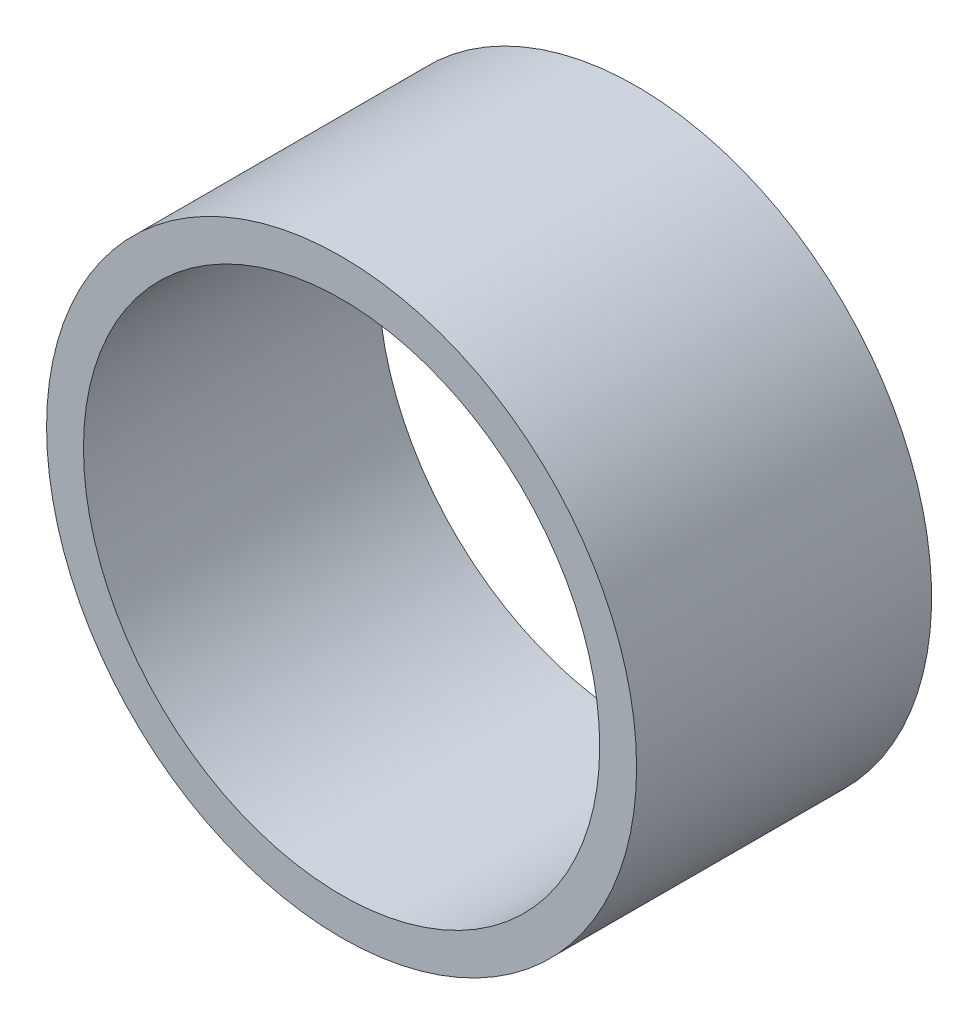
SolidWorks part; units mm, degrees
ref_plane "Front Plane" through (0, 0, 0) normal (0, 0, 1) x (1, 0, 0)
ref_plane "Top Plane" through (0, 0, 0) normal (0, 1, 0) x (1, 0, 0)
ref_plane "Right Plane" through (0, 0, 0) normal (1, 0, 0) x (0, 0, -1)
sketch "Sketch1" plane through (0, 0, 0) normal (0, 0, 1) x (1, 0, 0)
  circle A0 centre (0, 0) radius 12.7
  circle A1 centre (0, 0) radius 11.1125
  dimension "D1" = 22.225
  dimension "D2" = 25.4
extrude "Boss-Extrude1" add sketch "Sketch1" along normal blind 457.2
sketch "Sketch2" plane through (0, 0, 0) normal (0, 1, 0) x (1, 0, 0)
  line L0 (-11.1125, -457.2) -> (11.1125, -457.2) construction
  line L1 (-123.6881, -444.5) -> (178.817, -444.5)
  line L2 (-123.6881, -444.5) -> (-123.6881, 58.8853)
  line L3 (-123.6881, 58.8853) -> (178.817, 58.8853)
  line L4 (178.817, -444.5) -> (178.817, 58.8853)
  dimension "D1" = 12.7
extrude "Cut-Extrude1" cut sketch "Sketch2" against normal blind 25.4 and the other way blind 25.4
